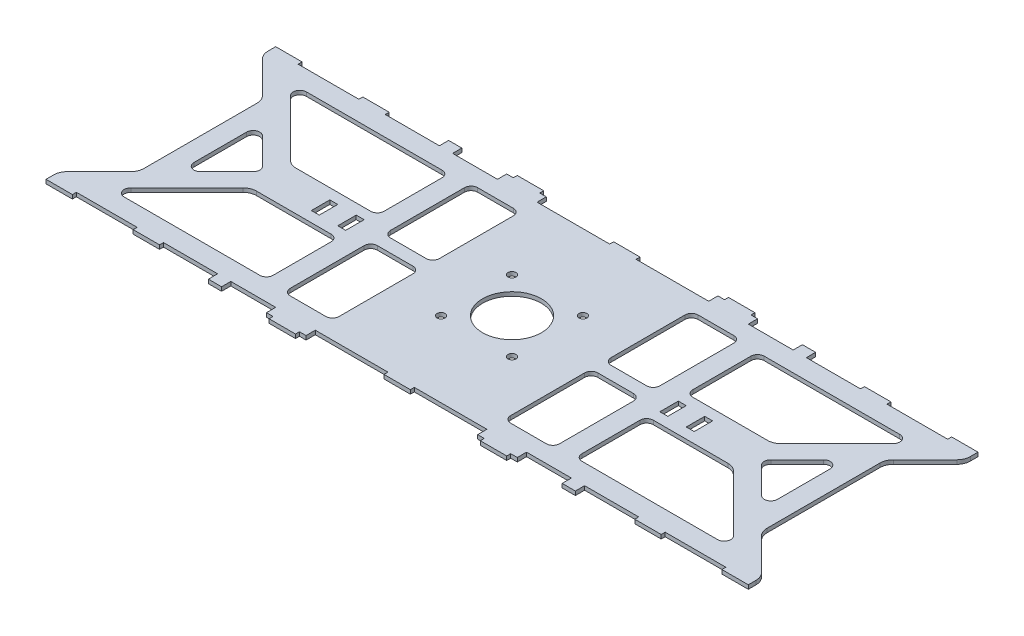
SolidWorks part; units mm, degrees
material "1023 Arkusz stali węglowej (SS)"
ref_plane "Płaszczyzna przednia" through (0, 0, 0) normal (0, 0, 1) x (1, 0, 0)
ref_plane "Płaszczyzna górna" through (0, 0, 0) normal (0, 1, 0) x (1, 0, 0)
ref_plane "Płaszczyzna prawa" through (0, 0, 0) normal (1, 0, 0) x (0, 0, -1)
sketch "Szkic1" plane through (0, 0, 0) normal (0, 1, 0) x (1, 0, 0)
  line L214 (263.0711, -74.0711) -> (238.9289, -49.9289)
  line L215 (236, -42.8579) -> (236, 0)
  line L216 (266, -87) -> (266, -81.1421)
  line L217 (246, -87) -> (246, -84)
  line L218 (200, -84) -> (200, -87)
  line L219 (200, -87) -> (180, -87)
  line L220 (180, -87) -> (180, -84)
  line L221 (246, -84) -> (200, -84)
  line L222 (266, -87) -> (246, -87)
  line L223 (180, -84) -> (139, -84)
  line L224 (139, -84) -> (139, -91)
  line L225 (139, -91) -> (129, -91)
  line L226 (129, -91) -> (129, -84)
  line L227 (129, -84) -> (95, -84)
  line L228 (90, -94) -> (70, -94)
  line L229 (90, -91) -> (90, -94)
  line L230 (70, -91) -> (70, -94)
  line L231 (95, -91) -> (95, -84)
  line L232 (65, -91) -> (65, -84)
  line L233 (90, -91) -> (95, -91)
  line L234 (65, -91) -> (70, -91)
  line L235 (65, -84) -> (10, -84)
  line L236 (10, -84) -> (10, -87)
  line L237 (10, -87) -> (0, -87)
  line L238 (145, 0) -> (145, -7)
  line L239 (125, -7) -> (119, -7)
  line L240 (119, -7) -> (119, 0)
  line L241 (125, 0) -> (125, -7)
  line L242 (139, 0) -> (139, -7)
  line L243 (145, -7) -> (139, -7)
  line L244 (65, -10) -> (65, -66)
  line L245 (97, -5) -> (70, -5)
  line L246 (102, -66) -> (102, -10)
  line L247 (70, -71) -> (97, -71)
  line L248 (178.6447, -15) -> (122, -15)
  line L249 (228.2513, -60.4645) -> (185.7157, -17.9289)
  line L250 (224.7157, -69) -> (122, -69)
  line L251 (117, -64) -> (117, -20)
  line L252 (212.4645, -23.4645) -> (192.5355, -3.5355)
  line L253 (221, -19.9289) -> (221, 0)
  line L254 (263.0711, 74.0711) -> (238.9289, 49.9289)
  line L255 (236, 42.8579) -> (236, 0)
  line L256 (266, 87) -> (266, 81.1421)
  line L257 (246, 87) -> (246, 84)
  line L258 (200, 84) -> (200, 87)
  line L259 (200, 87) -> (180, 87)
  line L260 (180, 87) -> (180, 84)
  line L261 (246, 84) -> (200, 84)
  line L262 (266, 87) -> (246, 87)
  line L263 (180, 84) -> (139, 84)
  line L264 (139, 84) -> (139, 91)
  line L265 (139, 91) -> (129, 91)
  line L266 (129, 91) -> (129, 84)
  line L267 (129, 84) -> (95, 84)
  line L268 (90, 94) -> (70, 94)
  line L269 (90, 91) -> (90, 94)
  line L270 (70, 91) -> (70, 94)
  line L271 (95, 91) -> (95, 84)
  line L272 (65, 91) -> (65, 84)
  line L273 (90, 91) -> (95, 91)
  line L274 (65, 91) -> (70, 91)
  line L275 (65, 84) -> (10, 84)
  line L276 (10, 84) -> (10, 87)
  line L277 (10, 87) -> (0, 87)
  line L278 (145, 0) -> (145, 7)
  line L279 (125, 7) -> (119, 7)
  line L280 (119, 7) -> (119, 0)
  line L281 (125, 0) -> (125, 7)
  line L282 (139, 0) -> (139, 7)
  line L283 (145, 7) -> (139, 7)
  line L284 (65, 10) -> (65, 66)
  line L285 (97, 5) -> (70, 5)
  line L286 (102, 66) -> (102, 10)
  line L287 (70, 71) -> (97, 71)
  line L288 (178.6447, 15) -> (122, 15)
  line L289 (228.2513, 60.4645) -> (185.7157, 17.9289)
  line L290 (224.7157, 69) -> (122, 69)
  line L291 (117, 64) -> (117, 20)
  line L292 (212.4645, 23.4645) -> (192.5355, 3.5355)
  line L293 (221, 19.9289) -> (221, 0)
  line L294 (-263.0711, 74.0711) -> (-238.9289, 49.9289)
  line L295 (-236, 42.8579) -> (-236, 0)
  line L296 (-266, 87) -> (-266, 81.1421)
  line L297 (-246, 87) -> (-246, 84)
  line L298 (-200, 84) -> (-200, 87)
  line L299 (-200, 87) -> (-180, 87)
  line L300 (-180, 87) -> (-180, 84)
  line L301 (-246, 84) -> (-200, 84)
  line L302 (-266, 87) -> (-246, 87)
  line L303 (-180, 84) -> (-139, 84)
  line L304 (-139, 84) -> (-139, 91)
  line L305 (-139, 91) -> (-129, 91)
  line L306 (-129, 91) -> (-129, 84)
  line L307 (-129, 84) -> (-95, 84)
  line L308 (-90, 94) -> (-70, 94)
  line L309 (-90, 91) -> (-90, 94)
  line L310 (-70, 91) -> (-70, 94)
  line L311 (-95, 91) -> (-95, 84)
  line L312 (-65, 91) -> (-65, 84)
  line L313 (-90, 91) -> (-95, 91)
  line L314 (-65, 91) -> (-70, 91)
  line L315 (-65, 84) -> (-10, 84)
  line L316 (-10, 84) -> (-10, 87)
  line L317 (-10, 87) -> (0, 87)
  line L318 (-145, 0) -> (-145, 7)
  line L319 (-125, 7) -> (-119, 7)
  line L320 (-119, 7) -> (-119, 0)
  line L321 (-125, 0) -> (-125, 7)
  line L322 (-139, 0) -> (-139, 7)
  line L323 (-145, 7) -> (-139, 7)
  line L324 (-65, 10) -> (-65, 66)
  line L325 (-97, 5) -> (-70, 5)
  line L326 (-102, 66) -> (-102, 10)
  line L327 (-70, 71) -> (-97, 71)
  line L328 (-178.6447, 15) -> (-122, 15)
  line L329 (-228.2513, 60.4645) -> (-185.7157, 17.9289)
  line L330 (-224.7157, 69) -> (-122, 69)
  line L331 (-117, 64) -> (-117, 20)
  line L332 (-212.4645, 23.4645) -> (-192.5355, 3.5355)
  line L333 (-221, 19.9289) -> (-221, 0)
  line L334 (-263.0711, -74.0711) -> (-238.9289, -49.9289)
  line L335 (-236, -42.8579) -> (-236, 0)
  line L336 (-266, -87) -> (-266, -81.1421)
  line L337 (-246, -87) -> (-246, -84)
  line L338 (-200, -84) -> (-200, -87)
  line L339 (-200, -87) -> (-180, -87)
  line L340 (-180, -87) -> (-180, -84)
  line L341 (-246, -84) -> (-200, -84)
  line L342 (-266, -87) -> (-246, -87)
  line L343 (-180, -84) -> (-139, -84)
  line L344 (-139, -84) -> (-139, -91)
  line L345 (-139, -91) -> (-129, -91)
  line L346 (-129, -91) -> (-129, -84)
  line L347 (-129, -84) -> (-95, -84)
  line L348 (-90, -94) -> (-70, -94)
  line L349 (-90, -91) -> (-90, -94)
  line L350 (-70, -91) -> (-70, -94)
  line L351 (-95, -91) -> (-95, -84)
  line L352 (-65, -91) -> (-65, -84)
  line L353 (-90, -91) -> (-95, -91)
  line L354 (-65, -91) -> (-70, -91)
  line L355 (-65, -84) -> (-10, -84)
  line L356 (-10, -84) -> (-10, -87)
  line L357 (-10, -87) -> (0, -87)
  line L358 (-145, 0) -> (-145, -7)
  line L359 (-125, -7) -> (-119, -7)
  line L360 (-119, -7) -> (-119, 0)
  line L361 (-125, 0) -> (-125, -7)
  line L362 (-139, 0) -> (-139, -7)
  line L363 (-145, -7) -> (-139, -7)
  line L364 (-65, -10) -> (-65, -66)
  line L365 (-97, -5) -> (-70, -5)
  line L366 (-102, -66) -> (-102, -10)
  line L367 (-70, -71) -> (-97, -71)
  line L368 (-178.6447, -15) -> (-122, -15)
  line L369 (-228.2513, -60.4645) -> (-185.7157, -17.9289)
  line L370 (-224.7157, -69) -> (-122, -69)
  line L371 (-117, -64) -> (-117, -20)
  line L372 (-212.4645, -23.4645) -> (-192.5355, -3.5355)
  line L373 (-221, -19.9289) -> (-221, 0)
  arc A106 (70, -5) -> (65, -10) centre (70, -10) ccw
  arc A107 (97, -71) -> (102, -66) centre (97, -66) ccw
  arc A108 (102, -10) -> (97, -5) centre (97, -10) ccw
  arc A109 (65, -66) -> (70, -71) centre (70, -66) ccw
  arc A110 (0, -22.3) -> (22.3, 0) centre (0, 0) ccw
  arc A111 (122, -15) -> (117, -20) centre (122, -20) ccw
  arc A112 (224.7157, -69) -> (228.2513, -60.4645) centre (224.7157, -64) ccw
  arc A113 (117, -64) -> (122, -69) centre (122, -64) ccw
  arc A114 (212.4645, -23.4645) -> (221, -19.9289) centre (216, -19.9289) ccw
  arc A115 (191.0711, 0) -> (192.5355, -3.5355) centre (196.0711, 0) ccw
  arc A116 (185.7157, -17.9289) -> (178.6447, -15) centre (178.6447, -25) ccw
  arc A117 (266, -81.1421) -> (263.0711, -74.0711) centre (256, -81.1421) ccw
  arc A118 (236, -42.8579) -> (238.9289, -49.9289) centre (246, -42.8579) ccw
  circle A119 centre (26.8701, -26.8701) radius 3
  arc A120 (65, 10) -> (70, 5) centre (70, 10) ccw
  arc A121 (102, 66) -> (97, 71) centre (97, 66) ccw
  arc A122 (97, 5) -> (102, 10) centre (97, 10) ccw
  arc A123 (70, 71) -> (65, 66) centre (70, 66) ccw
  arc A124 (22.3, 0) -> (0, 22.3) centre (0, 0) ccw
  arc A125 (117, 20) -> (122, 15) centre (122, 20) ccw
  arc A126 (228.2513, 60.4645) -> (224.7157, 69) centre (224.7157, 64) ccw
  arc A127 (122, 69) -> (117, 64) centre (122, 64) ccw
  arc A128 (221, 19.9289) -> (212.4645, 23.4645) centre (216, 19.9289) ccw
  arc A129 (192.5355, 3.5355) -> (191.0711, 0) centre (196.0711, 0) ccw
  arc A130 (178.6447, 15) -> (185.7157, 17.9289) centre (178.6447, 25) ccw
  arc A131 (263.0711, 74.0711) -> (266, 81.1421) centre (256, 81.1421) ccw
  arc A132 (238.9289, 49.9289) -> (236, 42.8579) centre (246, 42.8579) ccw
  circle A133 centre (26.8701, 26.8701) radius 3
  arc A134 (-70, 5) -> (-65, 10) centre (-70, 10) ccw
  arc A135 (-97, 71) -> (-102, 66) centre (-97, 66) ccw
  arc A136 (-102, 10) -> (-97, 5) centre (-97, 10) ccw
  arc A137 (-65, 66) -> (-70, 71) centre (-70, 66) ccw
  arc A138 (0, 22.3) -> (-22.3, 0) centre (0, 0) ccw
  arc A139 (-122, 15) -> (-117, 20) centre (-122, 20) ccw
  arc A140 (-224.7157, 69) -> (-228.2513, 60.4645) centre (-224.7157, 64) ccw
  arc A141 (-117, 64) -> (-122, 69) centre (-122, 64) ccw
  arc A142 (-212.4645, 23.4645) -> (-221, 19.9289) centre (-216, 19.9289) ccw
  arc A143 (-191.0711, 0) -> (-192.5355, 3.5355) centre (-196.0711, 0) ccw
  arc A144 (-185.7157, 17.9289) -> (-178.6447, 15) centre (-178.6447, 25) ccw
  arc A145 (-266, 81.1421) -> (-263.0711, 74.0711) centre (-256, 81.1421) ccw
  arc A146 (-236, 42.8579) -> (-238.9289, 49.9289) centre (-246, 42.8579) ccw
  circle A147 centre (-26.8701, 26.8701) radius 3
  arc A148 (-65, -10) -> (-70, -5) centre (-70, -10) ccw
  arc A149 (-102, -66) -> (-97, -71) centre (-97, -66) ccw
  arc A150 (-97, -5) -> (-102, -10) centre (-97, -10) ccw
  arc A151 (-70, -71) -> (-65, -66) centre (-70, -66) ccw
  arc A152 (-22.3, 0) -> (0, -22.3) centre (0, 0) ccw
  arc A153 (-117, -20) -> (-122, -15) centre (-122, -20) ccw
  arc A154 (-228.2513, -60.4645) -> (-224.7157, -69) centre (-224.7157, -64) ccw
  arc A155 (-122, -69) -> (-117, -64) centre (-122, -64) ccw
  arc A156 (-221, -19.9289) -> (-212.4645, -23.4645) centre (-216, -19.9289) ccw
  arc A157 (-192.5355, -3.5355) -> (-191.0711, 0) centre (-196.0711, 0) ccw
  arc A158 (-178.6447, -15) -> (-185.7157, -17.9289) centre (-178.6447, -25) ccw
  arc A159 (-263.0711, -74.0711) -> (-266, -81.1421) centre (-256, -81.1421) ccw
  arc A160 (-238.9289, -49.9289) -> (-236, -42.8579) centre (-246, -42.8579) ccw
  circle A161 centre (-26.8701, -26.8701) radius 3
extrude "Dodanie-wyciągnięcie1" add sketch "Szkic1" along normal blind 3
